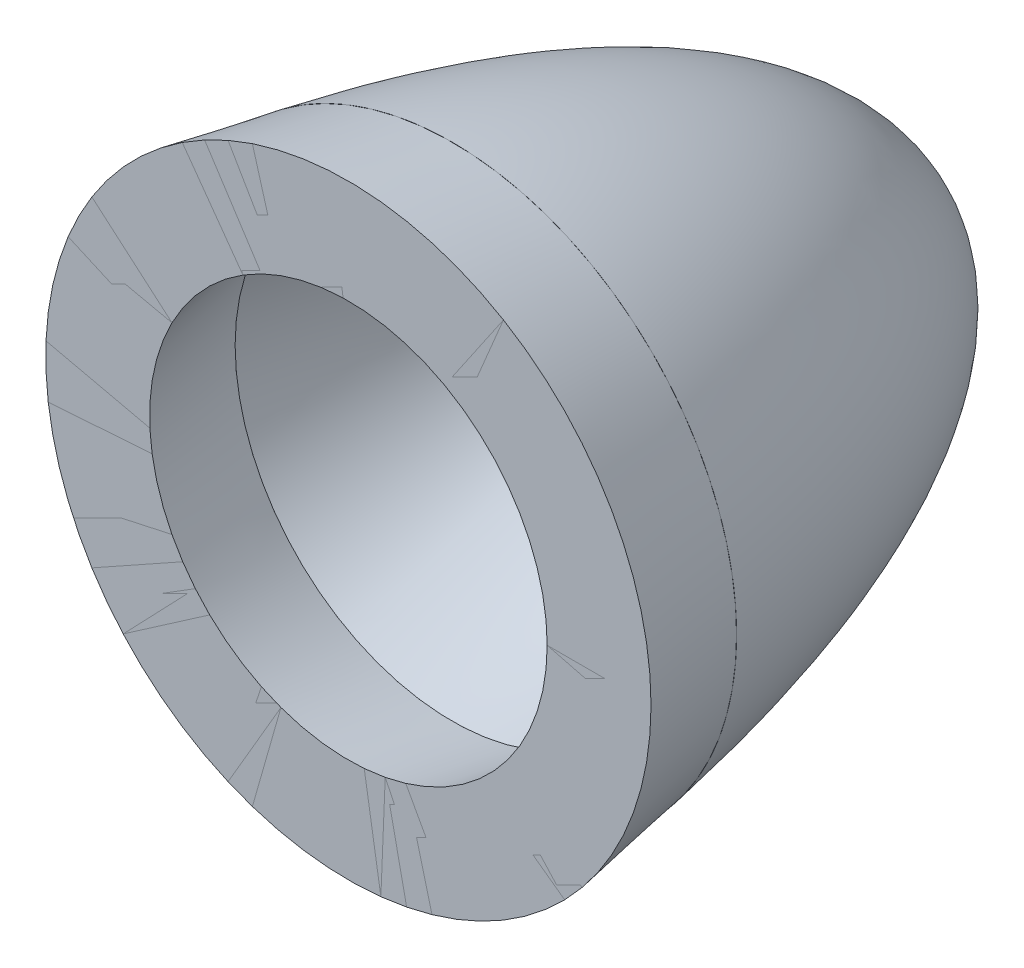
SolidWorks part; units mm, degrees
note: The reader was unsure of these and kept them because the rebuilt part matched: shared geometry of "Эскиз1<3>".
ref_plane "Спереди" through (0, 0, 0) normal (0, 0, 1) x (1, 0, 0)
ref_plane "Сверху" through (0, 0, 0) normal (0, 1, 0) x (1, 0, 0)
ref_plane "Справа" through (0, 0, 0) normal (1, 0, 0) x (0, 0, -1)
sketch "Эскиз1" plane through (0, 0, 0) normal (0, 0, 1) x (1, 0, 0)
  circle A0 centre (0, 0) radius 29.1429
  circle A1 centre (0, 0) radius 19.1429
  dimension "D1" = 10
surface "Поверхность-Заполнить1" sketch "Эскиз1"
extrude "Бобышка-Вытянуть1" add sketch "Эскиз1<3>" against normal blind 10 draft 10
sketch "Эскиз1<3>" plane through (0, 0, 0) normal (0, 0, 1) x (1, 0, 0) same geometry as "Эскиз1"
surface "Поверхность-Заполнить2"
surface "Поверхность-Заполнить4"
